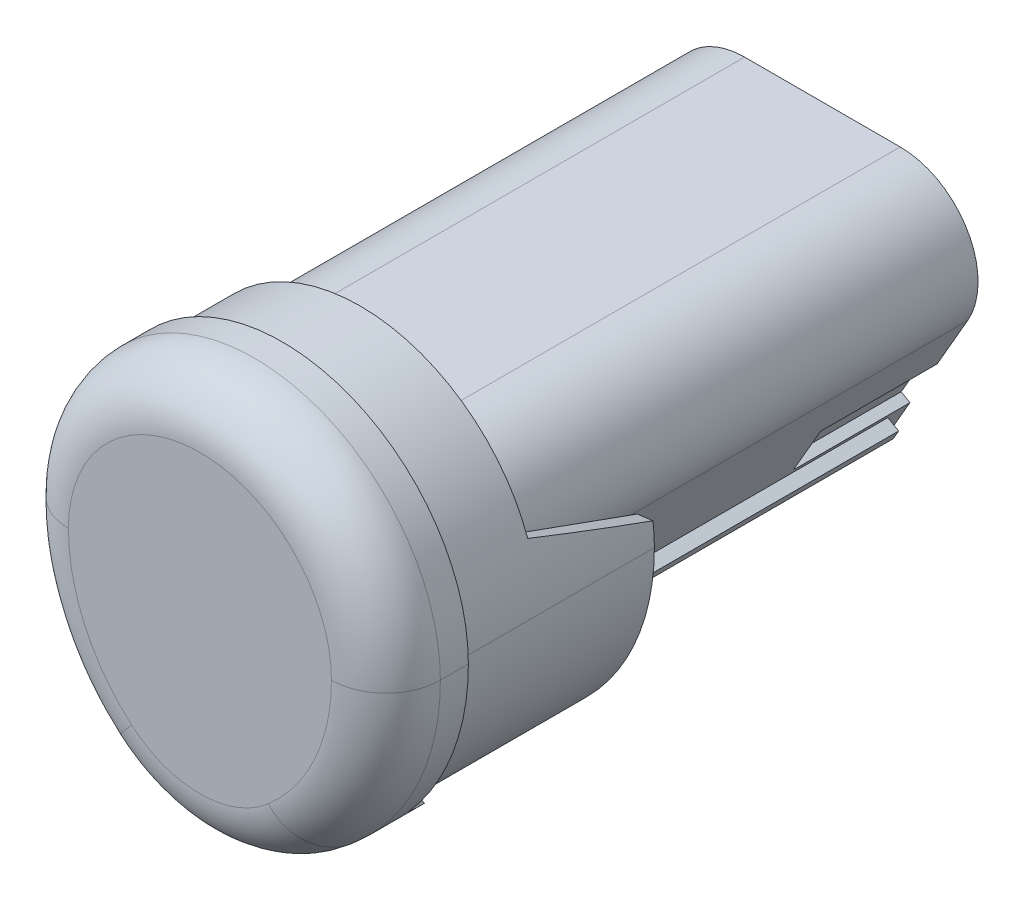
SolidWorks part; units mm, degrees
ref_plane "Plan de face" through (0, 0, 0) normal (0, 0, 1) x (1, 0, 0)
ref_plane "Plan de dessus" through (0, 0, 0) normal (0, 1, 0) x (1, 0, 0)
ref_plane "Plan de droite" through (0, 0, 0) normal (1, 0, 0) x (0, 0, -1)
ref_axis "Axe1" through (0, 0, 84) along (0, 0, -1)
sketch "Esquisse1" plane through (0, 0, 0) normal (0, 0, 1) x (1, 0, 0)
  line L0 (-10, 15.7735) -> (10, 15.7735)
  line L1 (-18.6603, 0.7735) -> (-8.6603, -16.547)
  line L2 (8.6603, -16.547) -> (18.6603, 0.7735)
  line L3 (-13.6603, -7.8868) -> (18.6603, 10.7735) construction
  line L4 (13.6603, -7.8868) -> (-18.6603, 10.7735) construction
  line L5 (0, -21.547) -> (0, 15.7735) construction
  line L6 (-20, 2.0501) -> (-20, 16.2695) construction
  line L7 (20, 1.5053) -> (20, 13.4658) construction
  line L8 (445.3732, -108.8997) -> (521.6093, -834.2377) construction
  line L9 (-7.7491, -6.7833) -> (-9.7491, -3.3192) construction
  line L10 (-7.7491, -6.7833) -> (-6.6232, -6.1333) construction
  line L11 (-9.7491, -3.3192) -> (-8.6232, -2.6692) construction
  line L12 (-6.6232, -6.1333) -> (-8.6232, -2.6692) construction
  line L13 (-7.7491, -6.7833) -> (-8.6232, -2.6692) construction
  line L14 (-9.7491, -3.3192) -> (-6.6232, -6.1333) construction
  arc A0 (-8.6603, -16.547) -> (8.6603, -16.547) centre (0, -11.547) ccw
  arc A1 (10, 15.7735) -> (18.6603, 0.7735) centre (10, 5.7735) cw
  arc A2 (-10, 15.7735) -> (-18.6603, 0.7735) centre (-10, 5.7735) ccw
  circle A3 centre (-9.3904, 5.4216) radius 2.9644 construction
  point P15 (0, 0)
  point P26 (-8.1861, -4.7263)
  dimension "D1" = 10
  dimension "D2" = 40
  dimension "D3" = 1.3
  dimension "D4" = 4
extrude "Boss.-Extru.1" add sketch "Esquisse1" along normal blind 80
sketch "Esquisse2" plane through (0, 0, 80) normal (0, 0, 1) x (1, 0, 0)
  line L0 (-12681.8859, 1278.2104) -> (-12646.9605, 1282.3837) construction
  line L1 (-242.0525, 250.143) -> (-212.0525, 250.143) construction
  line L2 (30.4051, 69.3804) -> (25.1957, 98.9247) construction
  line L3 (0, -28.2265) -> (0, 23.7735) construction
  line L4 (-7.624, 23.7735) -> (-13.8216, 23.7735) construction
  line L5 (-9.437, -28.2265) -> (-46.2994, -28.2265) construction
  line L6 (-23.9, 23.7735) -> (-23.9, -28.2265) construction
  line L7 (0, 23.7735) -> (0, -28.2265)
  line L9 (0, -28.2265) -> (0, -21.547) construction
  line L10 (0, 23.7735) -> (0, 15.7735) construction
  arc A4 (-8.6603, -16.547) -> (8.6603, -16.547) centre (0, -11.547) ccw construction
  arc A5 (0, 23.7735) -> (-23.9, -0.1265) centre (0, -0.1265) ccw
  arc A6 (-23.9, -0.1265) -> (-13.3729, -23.2265) centre (6.7081, -0.1265) ccw
  arc A7 (-13.3729, -23.2265) -> (0, -28.2265) centre (0, -7.8431) ccw
  dimension "D3" = 23.9
  dimension "D5" = 8
  dimension "D6" = 5
  dimension "D1" = 35.1738
  dimension "D2" = 30
  dimension "D4" = 52
extrude "Boss.-Extru.2" add sketch "Esquisse2" against normal blind 10.6
mirror "Symétrie1" about plane through (0, 0, 0) normal (1, 0, 0) of "Boss.-Extru.2"
sketch "Esquisse4" plane through (0, 0, 69.4) normal (0, 0, -1) x (-1, 0, 0)
  arc A8 (-22.9, -0.1265) -> (-12.7168, -22.4718) centre (6.7081, -0.1265) ccw
  arc A10 (-12.7168, -22.4718) -> (12.7168, -22.4718) centre (0, -7.8431) ccw
  arc A11 (-12.7168, -22.4718) -> (12.7168, -22.4718) centre (0, -7.8431) ccw
  arc A16 (-22.9, -0.1265) -> (-12.7168, -22.4718) centre (6.7081, -0.1265) ccw
  arc A17 (12.7168, -22.4718) -> (22.9, -0.1265) centre (-6.7081, -0.1265) ccw
  arc A18 (12.7168, -22.4718) -> (22.9, -0.1265) centre (-6.7081, -0.1265) ccw
  arc A19 (22.9, -0.1265) -> (-22.9, -0.1265) centre (0, -0.1265) ccw
  arc A20 (22.9, -0.1265) -> (-22.9, -0.1265) centre (0, -0.1265) ccw
  dimension "D1" = 1
extrude "Boss.-Extru.3" add sketch "Esquisse4" along normal blind 10
sketch "Esquisse6" plane through (0, 0, 69.4) normal (0, 0, -1) x (-1, 0, 0)
  line L0 (0, -28.2265) -> (0, 23.7735) construction
  line L1 (14.75, -21.9532) -> (0, -13.4765)
  line L2 (0, -13.4765) -> (0, -28.2265)
  arc A0 (0, -28.2265) -> (13.3729, -23.2265) centre (0, -7.8431) ccw
  arc A1 (0, -28.2265) -> (13.3729, -23.2265) centre (0, -7.8431) ccw construction
  arc A2 (13.3729, -23.2265) -> (23.9, -0.1265) centre (-6.7081, -0.1265) ccw construction
  arc A3 (13.3729, -23.2265) -> (14.75, -21.9532) centre (-6.7081, -0.1265) ccw
  dimension "D1" = 14.75
  dimension "D2" = 14.75
extrude "Boss.-Extru.4" add sketch "Esquisse6" along normal blind 3.5
mirror "Symétrie2" about plane through (0, 0, 0) normal (1, 0, 0) of "Boss.-Extru.4"
chamfer "Chanfrein1" distance 2 distance2 3.5 2 edges at (-14.2993, -21.6942, 69.4) (14.2993, -21.6942, 69.4) first distance on face at (0, -5.5207, 69.4)
sketch "Esquisse7" plane through (0, 0, 59.4) normal (0, 0, -1) x (-1, 0, 0)
  line L0 (0, -27.2265) -> (0, 0) construction
  line L2 (10, 15.7735) -> (-10, 15.7735) construction
  line L3 (0, -27.2265) -> (0, 0)
  line L4 (0, 0) -> (22.7156, 2.7735)
  arc A0 (-12.7168, -22.4718) -> (12.7168, -22.4718) centre (0, -7.8431) ccw construction
  arc A1 (0, -27.2265) -> (12.7168, -22.4718) centre (0, -7.8431) ccw
  arc A2 (-12.7168, -22.4718) -> (12.7168, -22.4718) centre (0, -7.8431) ccw construction
  arc A3 (12.7168, -22.4718) -> (22.9, -0.1265) centre (-6.7081, -0.1265) ccw
  arc A4 (12.7168, -22.4718) -> (22.9, -0.1265) centre (-6.7081, -0.1265) ccw construction
  arc A5 (22.9, -0.1265) -> (22.7156, 2.7735) centre (0, -0.1265) ccw
  arc A6 (22.9, -0.1265) -> (-22.9, -0.1265) centre (0, -0.1265) ccw construction
  arc A7 (22.9, -0.1265) -> (-22.9, -0.1265) centre (0, -0.1265) ccw construction
  dimension "D1" = 13
extrude "Boss.-Extru.5" add sketch "Esquisse7" along normal blind 14.9
mirror "Symétrie4" about plane through (0, 0, 0) normal (1, 0, 0) of "Boss.-Extru.5"
chamfer "Chanfrein2" distance 5 distance2 14.9 2 edges at (-21.0591, 2.5712, 59.4) (21.0591, 2.5712, 59.4) first distance on face at (0, 11.1203, 59.4)
sketch "Esquisse8" plane through (0, 0, 0) normal (0, 0, -1) x (-1, 0, 0)
  line L0 (-18.6603, 0.7735) -> (-8.6603, -16.547) construction
  line L1 (18.6603, 0.7735) -> (8.6603, -16.547) construction
  line L2 (-10, 15.7735) -> (10, 15.7735) construction
  line L3 (-18.6603, 0.7735) -> (-8.6603, -16.547)
  line L4 (18.6603, 0.7735) -> (8.6603, -16.547)
  line L5 (-10, 15.7735) -> (10, 15.7735)
  line L6 (-20.7317, 2.5202) -> (-20.1083, 7.1382)
  line L7 (-16.0835, 13.9607) -> (-12.4653, 16.6493)
  line L8 (20.7317, 2.5202) -> (20.1083, 7.1382)
  line L9 (12.4653, 16.6493) -> (16.0835, 13.9607)
  arc A0 (-10, 15.7735) -> (-18.6603, 0.7735) centre (-10, 5.7735) ccw construction
  arc A1 (-8.6603, -16.547) -> (8.6603, -16.547) centre (0, -11.547) ccw construction
  arc A2 (18.6603, 0.7735) -> (10, 15.7735) centre (10, 5.7735) ccw construction
  arc A3 (-10, 15.7735) -> (-18.6603, 0.7735) centre (-10, 5.7735) ccw
  arc A4 (-8.6603, -16.547) -> (8.6603, -16.547) centre (0, -11.547) ccw
  arc A5 (18.6603, 0.7735) -> (10, 15.7735) centre (10, 5.7735) ccw
  arc A6 (16.0835, 13.9607) -> (20.1083, 7.1382) centre (10, 5.7735) cw
  arc A42 (-12.4653, 16.6493) -> (12.4653, 16.6493) centre (0, -0.1265) cw
  arc A43 (-10, 15.9735) -> (-18.8335, 0.6735) centre (-10, 5.7735) ccw construction
  arc A44 (18.8335, 0.6735) -> (10, 15.9735) centre (10, 5.7735) ccw construction
  arc A45 (-20.1083, 7.1382) -> (-16.0835, 13.9607) centre (-10, 5.7735) cw
  arc A50 (20.7317, 2.5202) -> (19.6527, 6.9857) centre (0, -0.1265) ccw
  arc A51 (20.9, -0.1265) -> (20.7317, 2.5202) centre (0, -0.1265) ccw
  arc A52 (11.4047, -20.9624) -> (20.9, -0.1265) centre (-6.7081, -0.1265) ccw
  arc A53 (-11.4047, -20.9624) -> (11.4047, -20.9624) centre (0, -7.8431) ccw
  arc A54 (-20.9, -0.1265) -> (-11.4047, -20.9624) centre (6.7081, -0.1265) ccw
  arc A55 (-20.7317, 2.5202) -> (-20.9, -0.1265) centre (0, -0.1265) ccw
  arc A56 (-19.6527, 6.9857) -> (-20.7317, 2.5202) centre (0, -0.1265) ccw
  arc A57 (19.6527, 6.9857) -> (-19.6527, 6.9857) centre (0, -0.1265) ccw
  arc A58 (20.7317, 2.5202) -> (19.6527, 6.9857) centre (0, -0.1265) ccw construction
  arc A59 (20.9, -0.1265) -> (20.7317, 2.5202) centre (0, -0.1265) ccw
  arc A60 (11.4047, -20.9624) -> (20.9, -0.1265) centre (-6.7081, -0.1265) ccw
  arc A61 (-11.4047, -20.9624) -> (11.4047, -20.9624) centre (0, -7.8431) ccw
  arc A62 (-20.9, -0.1265) -> (-11.4047, -20.9624) centre (6.7081, -0.1265) ccw
  arc A63 (-20.7317, 2.5202) -> (-20.9, -0.1265) centre (0, -0.1265) ccw
  arc A64 (-19.6527, 6.9857) -> (-20.7317, 2.5202) centre (0, -0.1265) ccw construction
  arc A65 (19.6527, 6.9857) -> (-19.6527, 6.9857) centre (0, -0.1265) ccw construction
  dimension "D2" = 0.2
  dimension "D1" = 2
extrude "Enlèv. mat.-Extru.1" cut sketch "Esquisse8" against normal offset from surface (61.9 mm away) 2.5 up to face at (0, 13.4185, 59.4) offset beyond the face yes
sketch "Esquisse9" plane through (0, 0, 0) normal (0, 0, -1) x (-1, 0, 0)
  line L0 (-10.2144, -13.8552) -> (-11.6, -14.6552)
  line L1 (-8.6603, -16.547) -> (-18.6603, 0.7735) construction
  line L2 (-11.6, -14.6552) -> (-12.3, -13.4428)
  line L3 (-12.3, -13.4428) -> (-10.9144, -12.6428)
  line L4 (-10.9144, -12.6428) -> (-10.2144, -13.8552)
  line L5 (0, 28.6) -> (0, -28.6) construction
  line L6 (10.9144, -12.6428) -> (10.2144, -13.8552)
  line L7 (12.3, -13.4428) -> (10.9144, -12.6428)
  line L8 (11.6, -14.6552) -> (12.3, -13.4428)
  line L9 (10.2144, -13.8552) -> (11.6, -14.6552)
  dimension "D1" = 1.6
  dimension "D2" = 1.4
  dimension "D3" = 24.6
extrude "Boss.-Extru.8" add sketch "Esquisse9" against normal up to next from offset 2.5 offset against normal yes
sketch "Esquisse10" plane through (0, 0, 0) normal (0, 0, -1) x (-1, 0, 0)
  line L0 (-11.25, -12.0614) -> (-10.1242, -11.4114)
  line L1 (-10.9144, -12.6428) -> (-18.6603, 0.7735) construction
  line L2 (-10.1242, -11.4114) -> (-13.6242, -5.3493)
  line L3 (-13.6242, -5.3493) -> (-14.75, -5.9993)
  line L4 (-8.6603, -16.547) -> (-18.6603, 0.7735) construction
  line L5 (-14.75, -5.9993) -> (-11.25, -12.0614)
  line L6 (11.25, -12.0614) -> (14.75, -5.9993)
  line L7 (18.6603, 0.7735) -> (10.9144, -12.6428) construction
  line L8 (18.6603, 0.7735) -> (8.6603, -16.547) construction
  line L9 (14.75, -5.9993) -> (13.6242, -5.3493)
  line L10 (13.6242, -5.3493) -> (10.1242, -11.4114)
  line L11 (10.1242, -11.4114) -> (11.25, -12.0614)
  dimension "D1" = 1.3
  dimension "D2" = 7
  dimension "D3" = 22.5
  dimension "D4" = 1.3
extrude "Enlèv. mat.-Extru.4" cut sketch "Esquisse10" against normal blind 15 contours L2 L3 L5 L0 | L11 L6 L9 L10
fillet "Congé1" radius 7 4 edges at (-21.1442, -12.8193, 80) (0, 23.7735, 80) (21.1442, -12.8193, 80) (0, -28.2265, 80)
